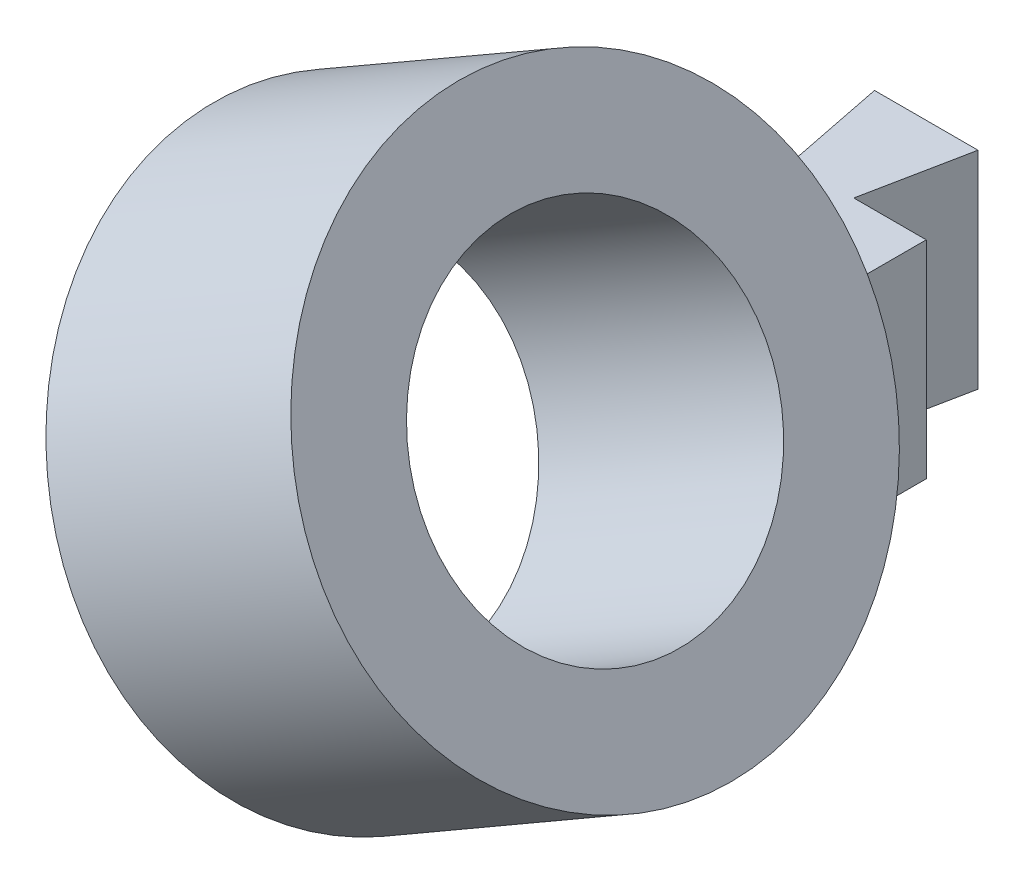
SolidWorks part; units mm, degrees
ref_plane "Front Plane" through (0, 0, 0) normal (0, 0, 1) x (1, 0, 0)
ref_plane "Top Plane" through (0, 0, 0) normal (0, 1, 0) x (1, 0, 0)
ref_plane "Right Plane" through (0, 0, 0) normal (1, 0, 0) x (0, 0, -1)
sketch "Sketch1" plane through (0, 0, 0) normal (0, 1, 0) x (1, 0, 0)
  line L0 (-3.5, 0) -> (-2.5, 5)
  line L1 (-2.5, 5) -> (-7.5, 5)
  line L2 (-7.5, 5) -> (-6.5, 0)
  line L3 (-6.5, 0) -> (-10, 0)
  line L4 (-10, 0) -> (-10, -2.85)
  line L5 (-10, -2.85) -> (0, -2.85)
  line L6 (0, -2.85) -> (0, 0)
  line L7 (0, 0) -> (-3.5, 0)
  line L8 (-5, 5) -> (-5, -2.85)
  point P11 (-3.3605, 0)
  point P12 (0, 0)
  dimension "D1" = 5
  dimension "D2" = 5
  dimension "D3" = 3
  dimension "D4" = 1.5
  dimension "D5" = 10
  dimension "D6" = 2.85
extrude "Boss-Extrude1" add sketch "Sketch1" along normal blind 10 contours L8 L1 L2 L3 L4 L5 | L1 L8 L5 L6 L7 L0 region at (-1.75, 0, 0.0931) region at (-5.0931, 0, -1.075)
sketch3d "3DSketch1" plane through (0, 0, 0) normal (0, 0, 1) x (1, 0, 0)
  dimension "D1" = 120
sketch "Sketch2" plane through (4.3301, 2.5, 0) normal (-0.866, -0.5, 0) x (0, 0, -1)
  line L6 (-2.85, -13.6603) -> (-2.85, -5) construction
  line L7 (-2.85, -8.6603) -> (0, -8.6603) construction
  circle A0 centre (-16, -8.6603) radius 13.15
  circle A1 centre (-16, -8.6603) radius 8.15
  point P3 (-26.7767, 0.6699)
  point P5 (0, 0)
  point P7 (0, 0)
  point P8 (10.55, 0)
  point P9 (-17.1912, -13.6603)
  point P12 (0, 0)
  dimension "D1" = 16.3
  dimension "D2" = 5
extrude "Boss-Extrude2" add sketch "Sketch2" along normal up to vertex (13.6603 mm away) separate body up to point (-10, 0, 2.85)
sketch "Sketch3" plane through (0, 0, 2.85) normal (0, 0, 1) x (1, 0, 0)
  line L4 (-10, 0) -> (0, 0)
  line L5 (0, 0) -> (0, 10)
  line L6 (0, 10) -> (-10, 10)
  line L7 (-10, 10) -> (-10, 0)
  line L8 (-10, 0) -> (0, 0)
  line L9 (0, 0) -> (0, 10)
  line L10 (0, 10) -> (-10, 10)
  line L11 (-10, 10) -> (-10, 0)
  dimension "D1" = 0
extrude "Boss-Extrude4" add sketch "Sketch3" along normal up to surface up to face at (-5.2551, -8.2184, 16)
equation "\"D4@Sketch1\"=\"D3@Sketch1\"/2"
equation "\"D6@Sketch1\"=16-13.15"
